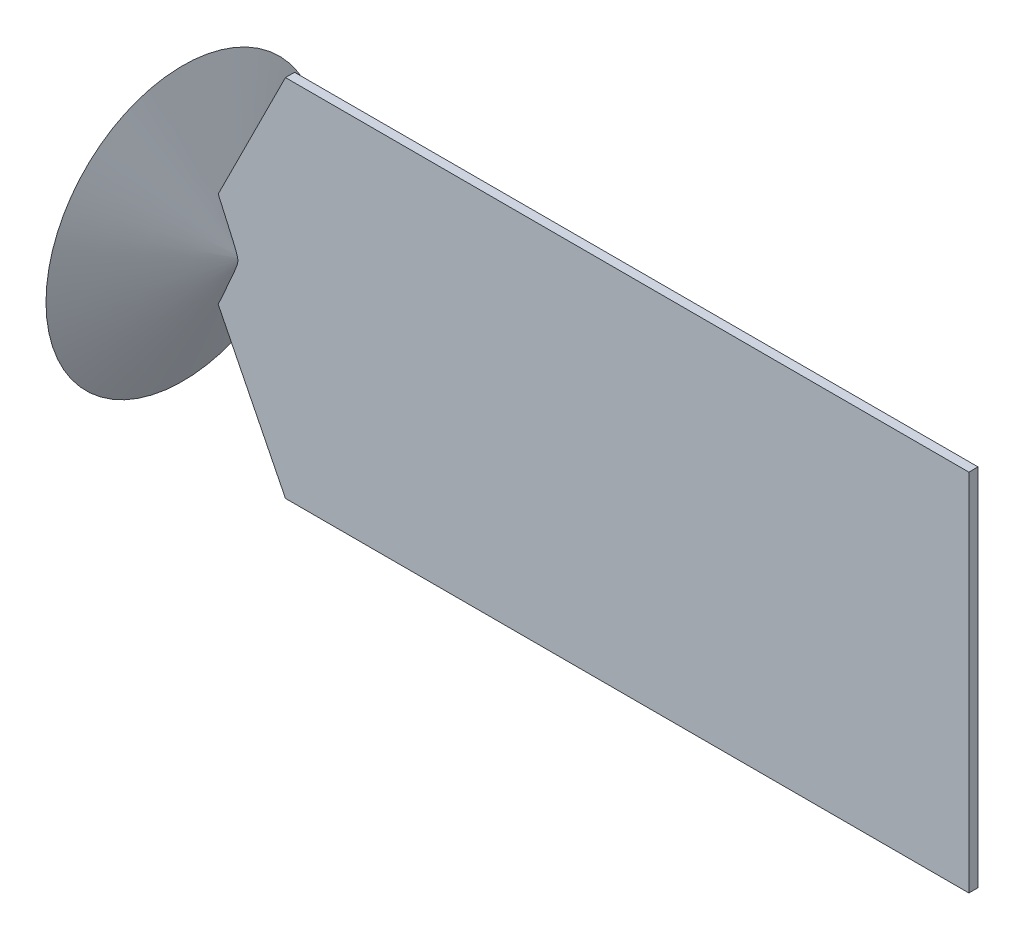
SolidWorks part; units mm, degrees
ref_plane "前视基准面" through (0, 0, 0) normal (0, 0, 1) x (1, 0, 0)
ref_plane "上视基准面" through (0, 0, 0) normal (0, 1, 0) x (1, 0, 0)
ref_plane "右视基准面" through (0, 0, 0) normal (1, 0, 0) x (0, 0, -1)
sketch "草图2" plane through (0, 0, 0) normal (0, 0, 1) x (1, 0, 0)
  line L0 (-1003.8117, 0) -> (49186.7727, 0) construction
  line L1 (0, -1003.8117) -> (0, 49186.7727) construction
  line L2 (-75, 40) -> (75, 40)
  line L3 (75, 40) -> (75, -40)
  line L5 (-75, -40) -> (75, -40)
  line L6 (-85, 0) -> (-98.555, 30)
  line L7 (-95, 0) -> (-75, 40)
  line L8 (-95, 0) -> (-75, -40)
  line L11 (-85, 0) -> (-98.555, 0)
  line L12 (-98.555, 30) -> (-98.555, 0)
  point P12 (75, 0)
  dimension "D1" = 150
  dimension "D2" = 80
  dimension "D3" = 40
  dimension "D4" = 75
  dimension "D5" = 170
  dimension "D6" = 10
  dimension "D8" = 30
extrude "凸台-拉伸2" add sketch "草图2" along normal mid plane 2 contours L7 L2 L3 L5 L8
revolve "旋转5" add sketch "草图2<5>" angle 360 mid plane about L0
sketch "草图2<5>" plane through (0, 0, 0) normal (0, 0, 1) x (1, 0, 0) same geometry as "草图2"
